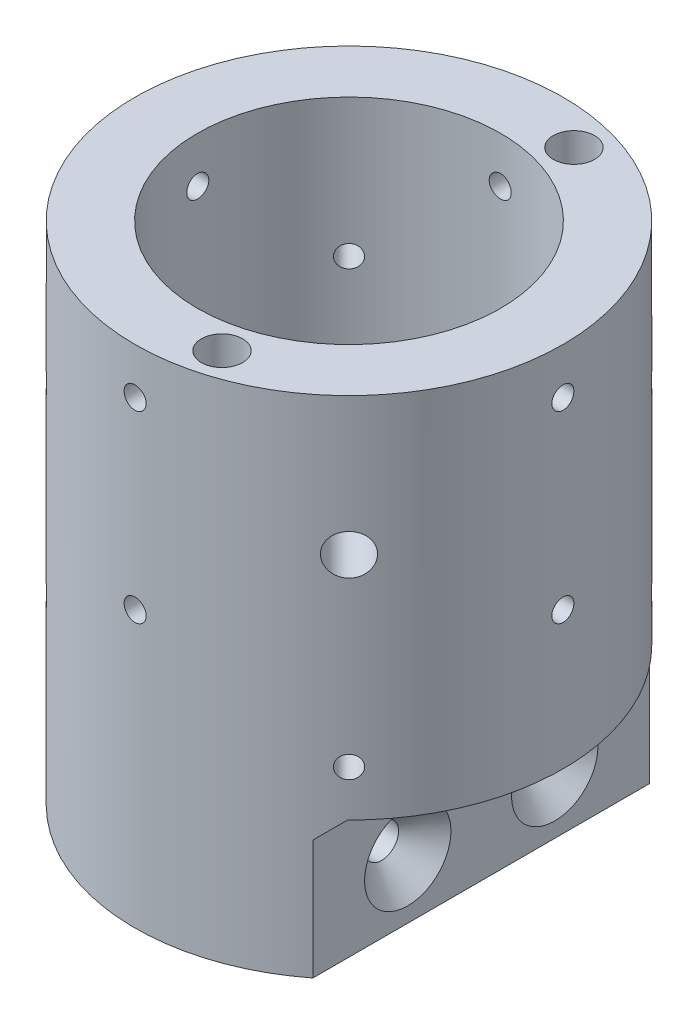
SolidWorks part; units mm, degrees
material "PLA плотность"
ref_plane "Спереди" through (0, 0, 0) normal (0, 0, 1) x (1, 0, 0)
ref_plane "Сверху" through (0, 0, 0) normal (0, 1, 0) x (1, 0, 0)
ref_plane "Справа" through (0, 0, 0) normal (1, 0, 0) x (0, 0, -1)
sketch "Эскиз1" plane through (0, 0, 0) normal (0, 1, 0) x (1, 0, 0)
  circle A0 centre (0, 0) radius 23.3
  dimension "D1" = 46.6
extrude "Бобышка-Вытянуть1" add sketch "Эскиз1" along normal blind 5
sketch "Эскиз2" plane through (0, 5, 0) normal (0, 1, 0) x (1, 0, 0)
  circle A0 centre (0, 0) radius 23.3
  circle A1 centre (0, 0) radius 16.5
  circle A2 centre (0, 0) radius 23.3 construction
  dimension "D1" = 33
  dimension "D2" = 0
extrude "Бобышка-Вытянуть2" add sketch "Эскиз2" along normal blind 35
chamfer "Фаска8" distance 2 angle 45 1 edges at (0, 5, 16.5)
sketch "Эскиз3" plane through (0, 0, 0) normal (1, 0, 0) x (0, 0, -1)
  line L0 (-23.3, 20) -> (28.0263, 20) construction
  line L1 (-23.3, 40) -> (-23.3, 0) construction
  line L2 (16.5, 40) -> (-16.5, 40) construction
  circle A1 centre (0, 35) radius 1.2
  dimension "D1" = 2.4
  dimension "D2" = 5
extrude "Вырез-Вытянуть1" cut sketch "Эскиз3" against normal through all
ref_plane "Плоскость1" through (0, 0, 0) normal (0.7071, 0, 0.7071) x (0, -1, 0)
sketch "Эскиз4" plane through (0, 0, 0) normal (0.7071, 0, 0.7071) x (0, -1, 0)
  line L0 (-20, 23.3) -> (-20, -30.0625) construction
  line L1 (0, 23.3) -> (-40, 23.3) construction
  line L3 (0, -23.3) -> (0, 23.3) construction
  circle A1 centre (-5, 0) radius 1.2
  dimension "D1" = 5
  dimension "D2" = 2.4
extrude "Вырез-Вытянуть2" cut sketch "Эскиз4" against normal through all from offset 16.3 offset against normal yes
pattern_circular "Круговой массив1" count 4 over 360 about axis through (0, 5, 0) along (0, -1, 0) of "Вырез-Вытянуть2"
pattern_circular "Круговой массив2" count 4 over 360 about axis through (0, 5, 0) along (0, -1, 0) of "Вырез-Вытянуть1"
pattern_linear "Линейный массив3" count 2 spacing 20 along (0, 1, 0) of "Круговой массив1"
pattern_linear "Линейный массив4" count 2 spacing 20 along (0, -1, 0) of "Круговой массив2"
sketch "Эскиз12" plane through (0, 0, 0) normal (0, -1, 0) x (1, 0, 0)
  line L1 (14.3923, 18.3235) -> (14.3923, -18.3235)
  line L20 (0, 15) -> (-2.7835, 17.7835)
  line L21 (-2.7835, -17.7835) -> (0, -15)
  line L22 (0, -15) -> (0, 15)
  line L23 (0, 15) -> (-2.7835, 17.7835)
  line L24 (-2.7835, -17.7835) -> (0, -15)
  line L25 (0, -15) -> (0, 15)
  circle A6 centre (0, 0) radius 23.3 construction
  arc A7 (14.3923, 18.3235) -> (14.3923, -18.3235) centre (0, 0) ccw
  arc A13 (-2.7835, 17.7835) -> (-2.7835, -17.7835) centre (0, 0) ccw
  arc A14 (-2.7835, 17.7835) -> (-2.7835, -17.7835) centre (0, 0) ccw
  dimension "D1" = 0
extrude "Бобышка-Вытянуть3" add sketch "Эскиз12" along normal blind 15 contours L1 region at (13.7929, 0, 0)
sketch "Эскиз13" plane through (0, -15, 0) normal (0, -1, 0) x (1, 0, 0)
  line L14 (-2.6786, -18.1029) -> (0.3, -15.1243)
  line L15 (0.3, 15.1243) -> (-2.6786, 18.1029)
  line L16 (0.3, -15.1243) -> (0.3, 15.1243)
  line L17 (-2.6786, -18.1029) -> (0.3, -15.1243)
  line L18 (0.3, 15.1243) -> (-2.6786, 18.1029)
  line L19 (0.3, -15.1243) -> (0.3, 15.1243)
  arc A5 (-2.6786, 18.1029) -> (-2.6786, -18.1029) centre (0, 0) ccw
  arc A6 (-2.6786, 18.1029) -> (-2.6786, -18.1029) centre (0, 0) ccw
  dimension "D1" = 0.3
extrude "Вырез-Вытянуть10" cut sketch "Эскиз13" against normal up to surface (15 mm away) up to face at (18.8461, 0, 0)
chamfer "Фаска4" distance 2 angle 45 1 edges at (14.3923, 0, 0)
chamfer "Фаска6" distance 2 angle 45 4 edges at (-1.1893, 0, -16.6136) (-18.3, 0, 0) (0.3, 0, 0) (-1.1893, 0, 16.6136)
chamfer "Фаска7" distance 2 angle 45 4 edges at (-1.1893, -15, -16.6136) (-18.3, -15, 0) (-1.1893, -15, 16.6136) (0.3, -15, 0)
hole_wizard "Зенковка для винта с полупотайной головкой M41" positions "Эскиз14" profile "Эскиз15" countersink size "M4" standard "ISO" end condition through all
sketch "Эскиз14" plane through (14.3923, -676.2045, -24.0267) normal (1, 0, 0) x (0, 0.0202, -0.9998)
  line L0 (-10.4265, 674.5519) -> (-10.6887, 661.5545) construction
  line L4 (-10.5576, 668.0532) -> (-20.4413, 668.0532) construction
  line L5 (-20.4413, 668.0532) -> (-1.8045, 668.0532) construction
  point P0 (-18.5576, 668.0532)
  point P19 (-2.5641, 667.7306)
sketch "Эскиз15" plane through (14.3923, -8.6613, 7.9984) normal (0, 1, 0) x (0, 0, -1)
  line L0 (0, 0) -> (0, 37.6923)
  line L1 (0, 37.6923) -> (1.85, 37.6923)
  line L2 (1.85, 37.6923) -> (1.85, 2.85)
  line L3 (1.85, 2.85) -> (4.7, 0)
  line L4 (4.7, 0) -> (0, 0)
  line L5 (-1.85, 2.85) -> (-4.7, 0) construction
  line L6 (0, -6.35) -> (0, 107.95) construction
  dimension "Диаметр сквозного отверстия" = 3.7
  dimension "Глубина сквозного отверстия" = 37.6923
  dimension "Диаметр передней зенковки" = 9.4
  dimension "Угол передней зенковки" = 90
sketch "Эскиз17" plane through (0, -15, 0) normal (0, -1, 0) x (1, 0, 0)
  circle A0 centre (5.3288, 0) radius 2.5
extrude "Вырез-Вытянуть11" cut sketch "Эскиз17" against normal blind 86
ref_plane "Плоскость2" through (0, 0, 0) normal (-0.7071, 0, -0.7071) x (-0.7071, 0, 0.7071)
sketch "Эскиз18" plane through (0, 0, 0) normal (-0.7071, 0, -0.7071) x (-0.7071, 0, 0.7071)
  circle A0 centre (0, 25) radius 1.2 construction
  circle A1 centre (0, 25) radius 1.2
  circle A2 centre (0, 25) radius 2.2
extrude "Вырез-Вытянуть12" cut sketch "Эскиз18" against normal blind 86
sketch "Эскиз21" plane through (0, -15, 0) normal (0, -1, 0) x (1, 0, 0)
  line L0 (5.3288, -15.6158) -> (5.3288, -22.6825) construction
  circle A0 centre (5.3288, -19.1491) radius 2.25
  circle A1 centre (0, 0) radius 16.5 construction
  circle A2 centre (0, 0) radius 16.5 construction
  arc A3 (14.3923, 18.3235) -> (14.3923, -18.3235) centre (0, 0) ccw construction
  dimension "D1" = 4.5
extrude "Вырез-Вытянуть13" cut sketch "Эскиз21" against normal through all
mirror "Зеркальное отражение1" about plane through (0, 0, 0) normal (0, 0, 1) of "Вырез-Вытянуть13"
